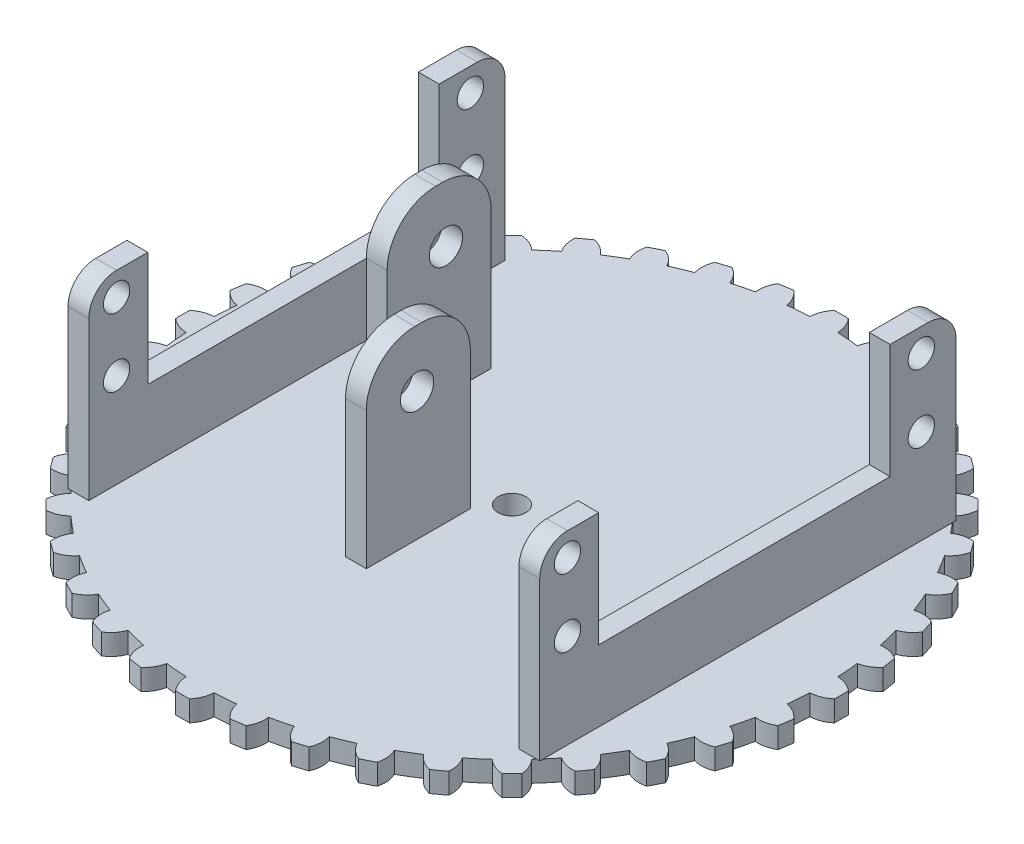
SolidWorks part; units mm, degrees
ref_plane "Front Plane" through (0, 0, 0) normal (0, 0, 1) x (1, 0, 0)
ref_plane "Top Plane" through (0, 0, 0) normal (0, 1, 0) x (1, 0, 0)
ref_plane "Right Plane" through (0, 0, 0) normal (1, 0, 0) x (0, 0, -1)
sketch "Sketch1" plane through (0, 0, 0) normal (0, 1, 0) x (1, 0, 0)
  circle A0 centre (0, 0) radius 45
  circle A1 centre (0, 0) radius 2
  dimension "D1" = 90
  dimension "D2" = 4
extrude "Boss-Extrude1" add sketch "Sketch1" along normal blind 3
sketch "Sketch2" plane through (0, 0, 0) normal (0, 1, 0) x (1, 0, 0)
  line L0 (0, 0) -> (0, 45) construction
  arc A6 (1, 47.4895) -> (-1, 47.4895) centre (0, 0) ccw
  arc A7 (-1, 47.4895) -> (-2, 44.9555) centre (1.9984, 44.8419) ccw
  circle A8 centre (0, 0) radius 45 construction
  arc A9 (1, 47.4895) -> (2, 44.9555) centre (-1.9984, 44.8419) cw
  circle A10 centre (0, 0) radius 45
  arc A11 (-2, 44.9555) -> (2, 44.9555) centre (0, 0) cw
  dimension "D1" = 95
  dimension "D4" = 4
  dimension "D2" = 2
  dimension "D3" = 1
extrude "Boss-Extrude2" add sketch "Sketch2" along normal blind 3 contours L0 | L0 | A11 A9 A6 A7
pattern_circular "CirPattern2" count 40 over 360 about axis through (0, 3, 0) along (0, -1, 0) of "Boss-Extrude2"
sketch "Sketch4" plane through (0, 3, 0) normal (0, 1, 0) x (1, 0, 0)
  line L0 (-34, 30) -> (34, 30)
  line L1 (-34, -25) -> (34, -25)
  line L2 (-34, -25) -> (-34, 25)
  line L3 (34, -25) -> (34, 25)
  line L4 (0, -25) -> (0, 25) construction
  line L6 (18, 25) -> (3, 25)
  line L7 (3, 25) -> (3, 17.5)
  line L8 (3, 17.5) -> (-14.15, 17.5)
  line L9 (-14.15, 17.5) -> (-14.15, 5)
  line L10 (-14.15, 5) -> (-34, 5)
  line L11 (-34, 5) -> (-34, -25)
  line L12 (-34, -25) -> (-31, -25)
  line L13 (-34, -25) -> (-34, 30)
  line L14 (-34, 30) -> (-31, 30)
  line L15 (-31, -25) -> (-31, 30)
  line L16 (34, 30) -> (31, 30)
  line L17 (31, -25) -> (31, 30)
  line L18 (34, -25) -> (31, -25)
  line L19 (34, -25) -> (34, 30)
  line L21 (-5.5, -18.5) -> (-2.5, -18.5)
  line L22 (-5.5, -18.5) -> (-5.5, -3.5)
  line L23 (-5.5, -3.5) -> (-2.5, -3.5)
  line L24 (-2.5, -18.5) -> (-2.5, -3.5)
  line L25 (-5.5, -18.5) -> (-2.5, -3.5) construction
  line L26 (-5.5, -3.5) -> (-2.5, -18.5) construction
  line L27 (-21.5, 15.5) -> (-18.5, 15.5)
  line L28 (-21.5, 15.5) -> (-21.5, 0.5)
  line L29 (-21.5, 0.5) -> (-18.5, 0.5)
  line L30 (-18.5, 15.5) -> (-18.5, 0.5)
  line L31 (-21.5, 15.5) -> (-18.5, 0.5) construction
  line L32 (-21.5, 0.5) -> (-18.5, 15.5) construction
  line L33 (-34, -25) -> (-31, -25)
  line L34 (-34, -25) -> (-34, -30)
  line L35 (-34, -30) -> (-31, -30)
  line L36 (-31, -25) -> (-31, -30)
  line L37 (34, -25) -> (31, -25)
  line L38 (34, -25) -> (31, -25)
  line L39 (34, -25) -> (34, -30)
  line L40 (34, -30) -> (31, -30)
  line L41 (31, -25) -> (31, -30)
  circle A1 centre (0, 0) radius 1.85
  point P9 (0, 0)
  point P19 (0, -25)
  point P25 (-1, -11)
  point P30 (-20, 8)
  point P36 (-4, -11)
  dimension "D1" = 50
  dimension "D2" = 68
  dimension "D4" = 55
  dimension "D5" = 3
  dimension "D6" = 15
  dimension "D7" = 3
  dimension "D8" = 14
  dimension "D9" = 19
  dimension "D10" = 15
  dimension "D11" = 3
  dimension "D12" = 11
  dimension "D13" = 3
  dimension "D14" = 5
  dimension "D15" = 5
extrude "Boss-Extrude3" add sketch "Sketch4" along normal blind 26.75 contours L10 L15 L14 L2 | L1 L15 L10 L2 | L17 L1 L3 L16 | L28 L27 L30 L29 | L22 L21 L24 L23 | L34 L33 L36 L35 | L13 L12 L15 L14 | L19 L16 L17 L18 | L39 L37 L41 L40 region at (-32.5, 3, -17.5) region at (32.5, 3, -2.5) region at (-32.5, 3, 10)
fillet "Fillet1" radius 4 4 edges at (-32.5, 29.75, -30) (32.5, 29.75, -30) (32.5, 29.75, 30) (-32.5, 29.75, 30)
sketch "Sketch5" plane through (-34, 0, 0) normal (-1, 0, 0) x (0, 0, 1)
  line L0 (-20.5, 29.75) -> (-20.5, 13.25)
  line L1 (26, 29.75) -> (-26, 29.75) construction
  line L2 (-20.5, 13.25) -> (21.5, 13.25)
  line L3 (21.5, 13.25) -> (21.5, 29.75)
  line L4 (21.5, 29.75) -> (-20.5, 29.75)
  line L5 (-30, 25.75) -> (-30, 3) construction
  line L6 (0.5, 13.25) -> (0.5, 29.75) construction
  line L7 (26, 29.75) -> (-26, 29.75) construction
  line L8 (-20.5, 21.5) -> (21.5, 21.5) construction
  circle A0 centre (-25, 26.4) radius 1.9
  circle A1 centre (26, 26.4) radius 1.9
  circle A2 centre (26, 16.6) radius 1.9
  circle A3 centre (-25, 16.6) radius 1.9
  point P11 (26, 16.6)
  point P22 (-25, 16.6)
  dimension "D4" = 3.8
  dimension "D1" = 9.5
  dimension "D2" = 42
  dimension "D3" = 13.25
  dimension "D5" = 4.5
  dimension "D6" = 3.35
extrude "Cut-Extrude1" cut sketch "Sketch5" against normal up to vertex (3 mm away) up to point (-31, 3, -30)
mirror "Mirror2" about plane through (0, 0, 0) normal (1, 0, 0) of "Cut-Extrude1"
sketch "Sketch7" plane through (-18.5, 0, 0) normal (1, 0, 0) x (0, 0, -1)
  line L0 (15.5, 3) -> (0.5, 3) construction
  circle A0 centre (8.9732, 21.5) radius 2.4
  dimension "D2" = 4.8
  dimension "D1" = 18.5
extrude "Cut-Extrude2" cut sketch "Sketch7" against normal up to next
sketch "Sketch8" plane through (-2.5, 0, 0) normal (1, 0, 0) x (0, 0, -1)
  line L0 (-18.5, 3) -> (-3.5, 3) construction
  circle A0 centre (-11.1873, 21.5) radius 2.4
  dimension "D1" = 4.8
  dimension "D2" = 18.5
extrude "Cut-Extrude3" cut sketch "Sketch8" against normal up to next
fillet "Fillet3" radius 7 4 edges at (-20, 29.75, -15.5) (-20, 29.75, -0.5) (-4, 29.75, 3.5) (-4, 29.75, 18.5)
